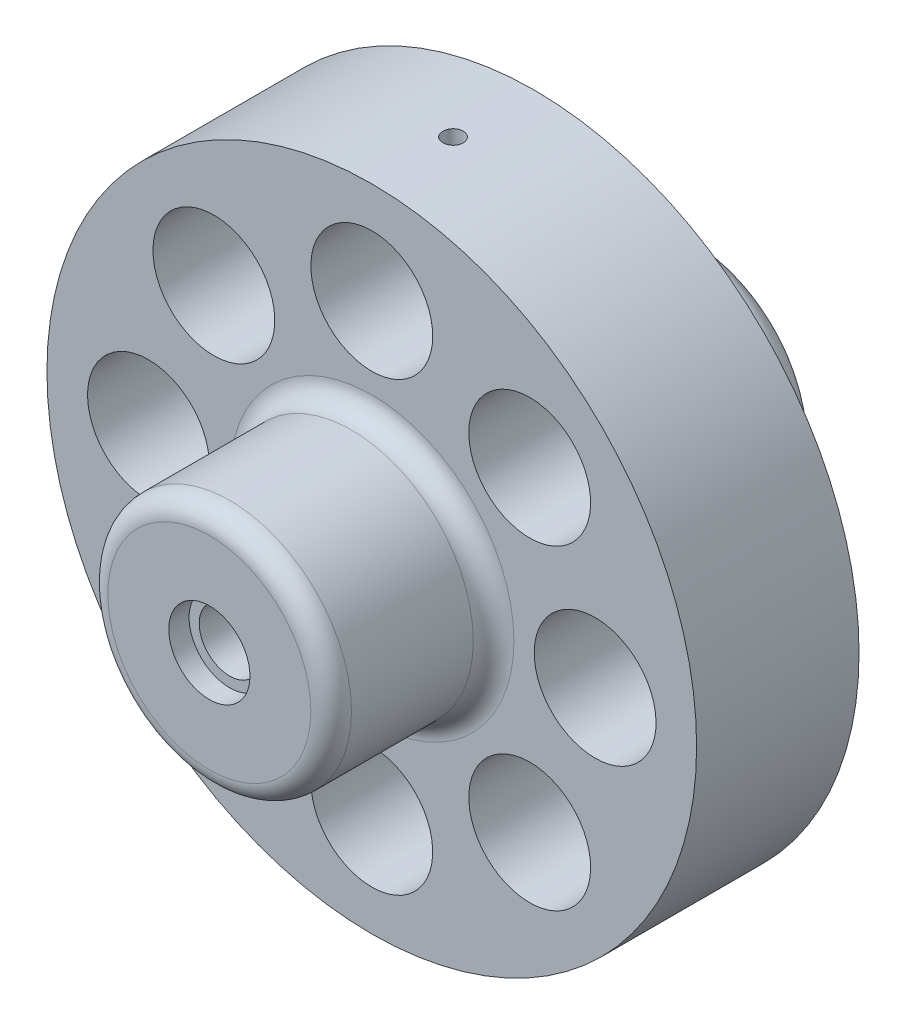
SolidWorks part; units mm, degrees
material "6061 Alloy"
ref_plane "Front Plane" through (0, 0, 0) normal (0, 0, 1) x (1, 0, 0)
ref_plane "Top Plane" through (0, 0, 0) normal (0, 1, 0) x (1, 0, 0)
ref_plane "Right Plane" through (0, 0, 0) normal (1, 0, 0) x (0, 0, -1)
sketch "Sketch1" plane through (0, 0, 0) normal (0, 0, 1) x (1, 0, 0)
  circle A0 centre (0, 0) radius 203.2
  dimension "D1" = 406.4
extrude "Boss-Extrude1" add sketch "Sketch1" along normal blind 101.6
sketch "Sketch2" [suppressed] plane through (0, 0, 101.6) normal (0, 0, 1) x (1, 0, 0)
  circle A0 centre (0, 0) radius 19.05
  dimension "D1" = 38.1
extrude "Cut-Extrude1" [suppressed] cut sketch "Sketch2" against normal blind 101.6
sketch "Sketch3" plane through (0, 0, 101.6) normal (0, 0, 1) x (1, 0, 0)
  circle A0 centre (0, 0) radius 76.2
  dimension "D1" = 152.4
extrude "Boss-Extrude2" add sketch "Sketch3" along normal blind 101.6 and the other way blind 203.2
sketch "Sketch4" plane through (0, 0, 203.2) normal (0, 0, 1) x (1, 0, 0)
  circle A0 centre (0, 0) radius 19.05
  dimension "D1" = 38.1
extrude "Cut-Extrude2" cut sketch "Sketch4" against normal through all
sketch "Sketch5" plane through (0, 0, 101.6) normal (0, 0, 1) x (1, 0, 0)
  circle A0 centre (0, 139.7) radius 38.1
  dimension "D1" = 76.2
  dimension "D2" = 139.7
extrude "Cut-Extrude3" cut sketch "Sketch5" against normal blind 101.6
ref_axis "Axis1" through (0, 0, -101.6) along (0, 0, 1)
pattern_circular "CirPattern1" count 8 over 360 about axis through (0, 0, -101.6) along (0, 0, 1) of "Cut-Extrude3"
fillet "Fillet1" radius 12.7 1 edges at (76.2, 0, 101.6)
fillet "Fillet2" radius 12.7 3 edges at (76.2, 0, -101.6) (76.2, 0, 0) (76.2, 0, 203.2)
ref_plane "Plane1" through (0, 203.2, 0) normal (0, 1, 0) x (-1, 0, 0)
sketch "Sketch6" plane through (0, 203.2, 0) normal (0, 1, 0) x (-1, 0, 0)
  line L0 (0, -101.6) -> (0, 203.2) construction
  line L1 (-203.2, 0) -> (203.2, 0) construction
  circle A0 centre (0, 50.8) radius 6.35
  dimension "D1" = 12.7
  dimension "D2" = 50.8
extrude "Cut-Extrude4" cut sketch "Sketch6" against normal up to next
ref_plane "Plane2" through (0, -203.2, 0) normal (0, -1, 0) x (1, 0, 0)
sketch "Sketch7" plane through (0, -203.2, 0) normal (0, -1, 0) x (1, 0, 0)
  line L0 (0, -101.6) -> (0, 203.2) construction
  line L1 (203.2, 101.6) -> (-203.2, 101.6) construction
  circle A0 centre (0, 50.8) radius 6.35
  dimension "D1" = 12.7
  dimension "D2" = 50.8
extrude "Cut-Extrude5" cut sketch "Sketch7" against normal up to next
sketch "Sketch8" plane through (0, 0, 203.2) normal (0, 0, 1) x (1, 0, 0)
  circle A0 centre (0, 0) radius 25.4
  dimension "D1" = 50.8
extrude "Cut-Extrude6" cut sketch "Sketch8" against normal blind 12.7
sketch "Sketch9" plane through (0, 0, -101.6) normal (0, 0, -1) x (-1, 0, 0)
  circle A0 centre (0, 0) radius 25.4
  dimension "D1" = 50.8
extrude "Cut-Extrude7" cut sketch "Sketch9" against normal blind 12.7
